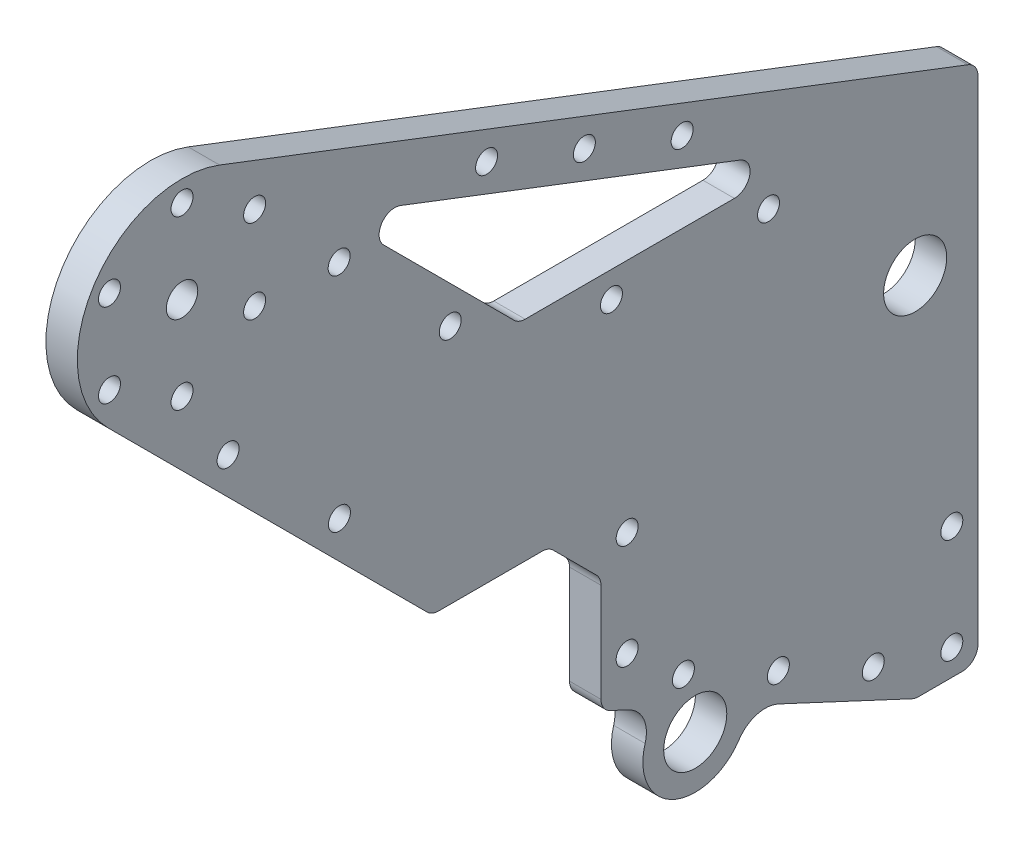
SolidWorks part; units mm, degrees
material "Thornel Mat VMA"
ref_plane "前视基准面" through (0, 0, 0) normal (0, 0, 1) x (1, 0, 0)
ref_plane "上视基准面" through (0, 0, 0) normal (0, 1, 0) x (1, 0, 0)
ref_plane "右视基准面" through (0, 0, 0) normal (1, 0, 0) x (0, 0, -1)
other "Configuration Table"
sketch "草图1" plane through (0, 0, 0) normal (1, 0, 0) x (0, 0, -1)
  line L0 (0, 0) -> (0, -70) construction
  line L1 (0, -70) -> (-120, -14.0431)
  line L2 (0, -70) -> (43.7623, -70) construction
  line L3 (-38.9711, 5.625) -> (-49.0211, 5.625) construction
  line L4 (-60, -42.0215) -> (-60, -14.9465) construction
  line L5 (-73.7711, 0.625) -> (-24.2711, 0.625) construction
  line L6 (-73.7711, 0.625) -> (-73.7711, 10.625) construction
  line L7 (-73.7711, 10.625) -> (-24.2711, 10.625) construction
  line L8 (-24.2711, 0.625) -> (-24.2711, 10.625) construction
  line L9 (-73.7711, 0.625) -> (-24.2711, 10.625) construction
  line L10 (-73.7711, 10.625) -> (-24.2711, 0.625) construction
  line L11 (-38.9711, -16.875) -> (0, -16.875) construction
  line L12 (12, -70) -> (12, 30)
  line L13 (-28.7711, -4.625) -> (-69.2711, -4.625) construction
  line L14 (-28.7711, -4.625) -> (-28.7711, 15.875) construction
  line L15 (-28.7711, 15.875) -> (-69.2711, 15.875) construction
  line L16 (-69.2711, -4.625) -> (-69.2711, 15.875) construction
  line L17 (-28.7711, -4.625) -> (-69.2711, 15.875) construction
  line L18 (-28.7711, 15.875) -> (-69.2711, -4.625) construction
  line L19 (0, -70) -> (12, -70)
  line L20 (-120, -10) -> (-120, -14.0431)
  line L21 (-120, 30) -> (12, 30)
  line L22 (0, -70) -> (-23.662, -70)
  line L23 (-23.662, -70) -> (-120, -25.0769)
  line L24 (-120, -25.0769) -> (-120, -14.0431)
  line L25 (-120, -10) -> (-60, -10)
  line L26 (-60, -10) -> (-60, -42.0215)
  line L27 (-70, -10) -> (-70, -37.3585)
  line L28 (-125.8579, 80.1421) -> (-75.7157, 30)
  line L29 (-154.1421, 51.8579) -> (-92.2843, -10)
  line L31 (1.395, 2.5273) -> (-1.4912, 2.4717) construction
  line L32 (-1.4912, 2.4717) -> (-2.8862, -0.0556) construction
  line L33 (-2.8862, -0.0556) -> (-1.395, -2.5273) construction
  line L34 (-1.395, -2.5273) -> (1.4912, -2.4717) construction
  line L35 (1.4912, -2.4717) -> (2.8862, 0.0556) construction
  line L36 (2.8862, 0.0556) -> (1.395, 2.5273) construction
  circle A0 centre (0, 0) radius 50.8 construction
  circle A1 centre (0, 0) radius 16.875 construction
  circle A2 centre (-38.9711, 5.625) radius 22.5 construction
  circle A3 centre (-120, 10) radius 20 construction
  circle A4 centre (-120, 10) radius 3
  circle A5 centre (0, 0) radius 6.025
  circle A6 centre (-73.7711, 10.625) radius 2.1 construction
  circle A7 centre (-73.7711, 0.625) radius 2.1 construction
  circle A8 centre (-24.2711, 10.625) radius 2.1 construction
  circle A9 centre (-24.2711, 0.625) radius 2.1 construction
  circle A10 centre (-140, 66) radius 20
  circle A11 centre (-38.9711, 5.625) radius 4 construction
  circle A12 centre (0, 0) radius 2.5 construction
  dimension "D1" = 101.6
  dimension "D2" = 33.75
  dimension "D3" = 45
  dimension "D6" = 40
  dimension "D7" = 6
  dimension "D9" = 12.05
  dimension "D13" = 4.2
  dimension "D17" = 120
  dimension "D18" = 10
  dimension "D21" = 40
  dimension "D22" = 70
  dimension "D23" = 136
  dimension "D25" = 8
  dimension "D26" = 5
  dimension "D4" = 65
  dimension "D5" = 70
  dimension "D8" = 60
  dimension "D10" = 10.05
  dimension "D11" = 10
  dimension "D12" = 49.5
  dimension "D14" = 20.5
  dimension "D15" = 40.5
  dimension "D16" = 12
  dimension "D19" = 10
  dimension "D20" = 10
  dimension "D24" = 135
extrude "凸台-拉伸1" add sketch "草图1" along normal mid plane 6 contours A3 A4 | A3 L25 L26 L1 L19 L12 L21 A9 A8 A7 A6 A5 L13 L16 L15 L14 | A10 region at (0, -0.5015, 49.3167) region at (0, 66, 140)
sketch "草图2" plane through (3, 0, 0) normal (1, 0, 0) x (0, 0, -1)
  line L0 (-140, 82) -> (-140, 66) construction
  circle A0 centre (-140, 66) radius 3
  circle A1 centre (-140, 82) radius 2.1
  circle A2 centre (-126.1436, 74) radius 2.1
  circle A3 centre (-126.1436, 58) radius 2.1
  circle A4 centre (-140, 50) radius 2.1
  circle A5 centre (-153.8564, 58) radius 2.1
  circle A6 centre (-153.8564, 74) radius 2.1
  point P17 (-140, 66)
  dimension "D1" = 6
  dimension "D2" = 4.2
  dimension "D3" = 16
  dimension "D4" = 6
extrude "切除-拉伸1" cut sketch "草图2" against normal blind 10
sketch "草图3" plane through (3, 0, 0) normal (1, 0, 0) x (0, 0, -1)
  circle A6 centre (0, 0) radius 8 construction
  circle A7 centre (0, 8) radius 1.6
  circle A8 centre (6.9282, 4) radius 1.6
  circle A9 centre (6.9282, -4) radius 1.6
  circle A10 centre (0, -8) radius 1.6
  circle A11 centre (-6.9282, -4) radius 1.6
  circle A12 centre (-6.9282, 4) radius 1.6
  point P18 (0, 0)
  dimension "D1" = 6
  dimension "D2" = 3.2
  dimension "D4" = 16
sketch "草图4" plane through (3, 0, 0) normal (1, 0, 0) x (0, 0, -1)
  line L0 (-60, -10) -> (-60, -42.0215) construction
  line L1 (-92.2843, -10) -> (-60, -10) construction
  line L2 (12, -70) -> (12, 30) construction
  line L4 (0, -70) -> (12, -70) construction
  line L5 (0, -70) -> (-60, -42.0215) construction
  circle A0 centre (-55, -15) radius 2.1
  circle A1 centre (-55, -35) radius 2.1
  circle A2 centre (7, -65) radius 2.1
  circle A3 centre (7, -45) radius 2.1
  circle A4 centre (-8, -60.7526) radius 2.1
  circle A5 centre (-26.1262, -52.3003) radius 2.1
  circle A6 centre (-44.2523, -43.8479) radius 2.1
  dimension "D1" = 4.2
  dimension "D2" = 5
  dimension "D3" = 5
  dimension "D5" = 4.2
  dimension "D6" = 5
  dimension "D7" = 5
  dimension "D9" = 4.2
  dimension "D10" = 5
  dimension "D11" = 20
  dimension "D4" = 2
  dimension "D8" = 2
  dimension "D12" = 3
extrude "切除-拉伸3" cut sketch "草图4" against normal blind 10
chamfer "倒角1" distance 10 angle 45 1 edges at (0, -10, 60)
fillet "圆角1" radius 3 8 edges at (0, 30, -12) (0, -70, -12) (0, -70, 0) (0, -42.0215, 60) (0, -20, 60) (0, -10, 70) (0, 30, 75.7157) (0, -10, 92.2843)
sketch "草图5" plane through (3, 0, 0) normal (1, 0, 0) x (0, 0, -1)
  line L0 (-110, 57.2132) -> (-88.7868, 36) construction
  line L1 (-125.8579, 80.1421) -> (-76.5944, 30.8787) construction
  line L2 (-95.4046, 49.6888) -> (-123.6525, 21.3683) construction
  line L3 (-154.1421, 51.8579) -> (-93.163, -9.1213) construction
  line L4 (-109.5286, 35.5286) -> (-99.6927, 25.7179) construction
  line L5 (-131.2143, 35.9443) -> (-109.9468, 14.7857) construction
  line L6 (-75.6211, 30.2284) -> (-74.4731, 33) construction
  line L7 (-58, 25) -> (-28, 25) construction
  line L8 (-74.4731, 30) -> (9, 30) construction
  line L9 (12, -67) -> (12, 27) construction
  circle A0 centre (-110, 57.2132) radius 2.1
  circle A1 centre (-88.7868, 36) radius 2.1
  circle A2 centre (-140, 66) radius 3 construction
  circle A3 centre (-109.9468, 14.7857) radius 2.1
  circle A4 centre (-131.2143, 35.9443) radius 2.1
  arc A5 (-76.5944, 30.8787) -> (-74.4731, 30) centre (-74.4731, 33) ccw construction
  circle A6 centre (-58, 25) radius 2.1
  circle A7 centre (-28, 25) radius 2.1
  dimension "D1" = 4.2
  dimension "D3" = 30
  dimension "D7" = 40
  dimension "D2" = 30
  dimension "D4" = 5
  dimension "D5" = 5
  dimension "D6" = 30
extrude "切除-拉伸4" cut sketch "草图5" against normal blind 10
extrude "切除-拉伸5" [suppressed] cut sketch "草图3" against normal blind 10
sketch "草图6" plane through (-3, 0, 0) normal (-1, 0, 0) x (0, 0, 1)
  line L10 (0.6028, -69.7189) -> (58.2679, -42.8293) construction
  line L11 (0.6028, -69.7189) -> (58.2679, -42.8293)
  line L20 (74.4731, 30) -> (-9, 30)
  line L21 (-12, 27) -> (-12, -67)
  line L22 (-9, -70) -> (-0.6651, -70)
  line L23 (0.6028, -69.7189) -> (26.0848, -57.8365)
  line L24 (54.786, -44.4529) -> (58.2679, -42.8293)
  line L25 (60, -40.1103) -> (60, -21.2426)
  line L26 (60.8787, -19.1213) -> (69.1213, -10.8787)
  line L27 (71.2426, -10) -> (91.0416, -10)
  line L28 (93.163, -9.1213) -> (154.1421, 51.8579)
  line L29 (125.8579, 80.1421) -> (76.5944, 30.8787)
  circle A1 centre (42, -54.5) radius 6.025
  arc A26 (-9, 30) -> (-12, 27) centre (-9, 27) ccw
  arc A27 (-12, -67) -> (-9, -70) centre (-9, -67) ccw
  arc A28 (-0.6651, -70) -> (0.6028, -69.7189) centre (-0.6651, -67) ccw
  arc A29 (33.6378, -59.9839) -> (26.0848, -57.8365) centre (28.6205, -63.2743) ccw
  arc A30 (33.6378, -59.9839) -> (51.5761, -51.6192) centre (42, -54.5) ccw
  arc A31 (54.786, -44.4529) -> (51.5761, -51.6192) centre (57.3217, -49.8907) ccw
  arc A32 (58.2679, -42.8293) -> (60, -40.1103) centre (57, -40.1103) ccw
  arc A33 (60.8787, -19.1213) -> (60, -21.2426) centre (63, -21.2426) ccw
  arc A34 (71.2426, -10) -> (69.1213, -10.8787) centre (71.2426, -13) ccw
  arc A35 (91.0416, -10) -> (93.163, -9.1213) centre (91.0416, -7) ccw
  arc A36 (154.1421, 51.8579) -> (125.8579, 80.1421) centre (140, 66) ccw
  arc A37 (74.4731, 30) -> (76.5944, 30.8787) centre (74.4731, 33) ccw
  line M50 (0.6028, -69.7189) -> (58.2679, -42.8293)
extrude "凸台-拉伸2" add sketch "草图6" against normal up to surface (6 mm away) contours A31 L11 A1 A29 A30 region at (-3, -55.8123, 31.254) up to face at (3, 57.2132, 107.9)
extrude "切除-拉伸6" cut sketch "草图6<3>" against normal through all both contours A1 M50 region at (-3, -50.2869, 40.0354)
sketch "草图6<3>" plane through (-3, 0, 0) normal (-1, 0, 0) x (0, 0, 1) same geometry as "草图6"
sketch "草图7" plane through (-3, 0, 0) normal (-1, 0, 0) x (0, 0, 1)
  line L12 (101.493, 55.7773) -> (76.5944, 30.8787)
  line L13 (74.4731, 30) -> (34.5248, 30)
  line L14 (33.4495, 35.8007) -> (98.2964, 60.6993)
  line L18 (132.8311, 84.671) -> (-10.0753, 29.8007)
  line L19 (-12, 27) -> (-12, -67)
  line L20 (-9, -70) -> (-0.6651, -70)
  line L21 (0.6028, -69.7189) -> (26.0848, -57.8365)
  line L22 (54.786, -44.4529) -> (58.2679, -42.8293)
  line L23 (60, -40.1103) -> (60, -21.2426)
  line L24 (60.8787, -19.1213) -> (69.1213, -10.8787)
  line L25 (71.2426, -10) -> (91.0416, -10)
  line L26 (93.163, -9.1213) -> (154.1421, 51.8579)
  line L34 (-12, 27) -> (-12, -67)
  line L35 (74.4731, 30) -> (-9, 30)
  line L36 (125.8579, 80.1421) -> (76.5944, 30.8787)
  line L37 (93.163, -9.1213) -> (154.1421, 51.8579)
  line L38 (71.2426, -10) -> (91.0416, -10)
  line L39 (60.8787, -19.1213) -> (69.1213, -10.8787)
  line L40 (60, -40.1103) -> (60, -21.2426)
  line L41 (54.786, -44.4529) -> (58.2679, -42.8293)
  line L42 (0.6028, -69.7189) -> (26.0848, -57.8365)
  line L43 (-9, -70) -> (-0.6651, -70)
  line L44 (-12, 27) -> (-12, -67)
  line L45 (74.4731, 30) -> (-9, 30)
  line L46 (125.8579, 80.1421) -> (76.5944, 30.8787)
  line L47 (93.163, -9.1213) -> (154.1421, 51.8579)
  line L48 (71.2426, -10) -> (91.0416, -10)
  line L49 (60.8787, -19.1213) -> (69.1213, -10.8787)
  line L50 (60, -40.1103) -> (60, -21.2426)
  line L51 (54.786, -44.4529) -> (58.2679, -42.8293)
  line L52 (0.6028, -69.7189) -> (26.0848, -57.8365)
  line L53 (-9, -70) -> (-0.6651, -70)
  circle A14 centre (81.8411, 59.737) radius 2.1
  circle A15 centre (63.1701, 52.5681) radius 2.1
  circle A16 centre (44.4991, 45.3992) radius 2.1
  arc A20 (101.493, 55.7773) -> (98.2964, 60.6993) centre (99.3717, 57.8986) ccw
  arc A21 (74.4731, 30) -> (76.5944, 30.8787) centre (74.4731, 33) ccw
  arc A22 (154.1421, 51.8579) -> (132.8311, 84.671) centre (140, 66) ccw
  arc A23 (-10.0753, 29.8007) -> (-12, 27) centre (-9, 27) ccw
  arc A24 (-12, -67) -> (-9, -70) centre (-9, -67) ccw
  arc A25 (-0.6651, -70) -> (0.6028, -69.7189) centre (-0.6651, -67) ccw
  arc A26 (33.6378, -59.9839) -> (26.0848, -57.8365) centre (28.6205, -63.2743) ccw
  arc A27 (33.6378, -59.9839) -> (51.5761, -51.6192) centre (42, -54.5) ccw
  arc A28 (54.786, -44.4529) -> (51.5761, -51.6192) centre (57.3217, -49.8907) ccw
  arc A29 (58.2679, -42.8293) -> (60, -40.1103) centre (57, -40.1103) ccw
  arc A30 (60.8787, -19.1213) -> (60, -21.2426) centre (63, -21.2426) ccw
  arc A31 (71.2426, -10) -> (69.1213, -10.8787) centre (71.2426, -13) ccw
  arc A32 (91.0416, -10) -> (93.163, -9.1213) centre (91.0416, -7) ccw
  arc A33 (33.4495, 35.8007) -> (34.5248, 30) centre (34.5248, 33) ccw
  arc A46 (-9, 30) -> (-12, 27) centre (-9, 27) ccw
  arc A47 (74.4731, 30) -> (76.5944, 30.8787) centre (74.4731, 33) ccw
  arc A48 (154.1421, 51.8579) -> (125.8579, 80.1421) centre (140, 66) ccw
  arc A49 (91.0416, -10) -> (93.163, -9.1213) centre (91.0416, -7) ccw
  arc A50 (71.2426, -10) -> (69.1213, -10.8787) centre (71.2426, -13) ccw
  arc A51 (60.8787, -19.1213) -> (60, -21.2426) centre (63, -21.2426) ccw
  arc A52 (58.2679, -42.8293) -> (60, -40.1103) centre (57, -40.1103) ccw
  arc A53 (54.786, -44.4529) -> (51.5761, -51.6192) centre (57.3217, -49.8907) ccw
  arc A54 (33.6378, -59.9839) -> (51.5761, -51.6192) centre (42, -54.5) ccw
  arc A55 (33.6378, -59.9839) -> (26.0848, -57.8365) centre (28.6205, -63.2743) ccw
  arc A56 (-0.6651, -70) -> (0.6028, -69.7189) centre (-0.6651, -67) ccw
  arc A57 (-12, -67) -> (-9, -70) centre (-9, -67) ccw
  arc A58 (-9, 30) -> (-12, 27) centre (-9, 27) ccw
  arc A59 (74.4731, 30) -> (76.5944, 30.8787) centre (74.4731, 33) ccw
  arc A60 (154.1421, 51.8579) -> (125.8579, 80.1421) centre (140, 66) ccw
  arc A61 (91.0416, -10) -> (93.163, -9.1213) centre (91.0416, -7) ccw
  arc A62 (71.2426, -10) -> (69.1213, -10.8787) centre (71.2426, -13) ccw
  arc A63 (60.8787, -19.1213) -> (60, -21.2426) centre (63, -21.2426) ccw
  arc A64 (58.2679, -42.8293) -> (60, -40.1103) centre (57, -40.1103) ccw
  arc A65 (54.786, -44.4529) -> (51.5761, -51.6192) centre (57.3217, -49.8907) ccw
  arc A66 (33.6378, -59.9839) -> (51.5761, -51.6192) centre (42, -54.5) ccw
  arc A67 (33.6378, -59.9839) -> (26.0848, -57.8365) centre (28.6205, -63.2743) ccw
  arc A68 (-0.6651, -70) -> (0.6028, -69.7189) centre (-0.6651, -67) ccw
  arc A69 (-12, -67) -> (-9, -70) centre (-9, -67) ccw
  line M64 (74.4731, 30) -> (-9, 30)
  arc M65 (-9, 30) -> (-12, 27) centre (-9, 27) ccw
  arc M83 (154.1421, 51.8579) -> (125.8579, 80.1421) centre (140, 66) ccw
  line M84 (125.8579, 80.1421) -> (76.5944, 30.8787)
  dimension "D1" = 0
extrude "凸台-拉伸3" add sketch "草图7" against normal up to surface (6 mm away) contours A33 L14 A20 L18 A16 A15 A14 M84 M83 M65 M64 region at (-3, 60.3664, 103.1714) up to face at (3, -54.5, 35.975)
